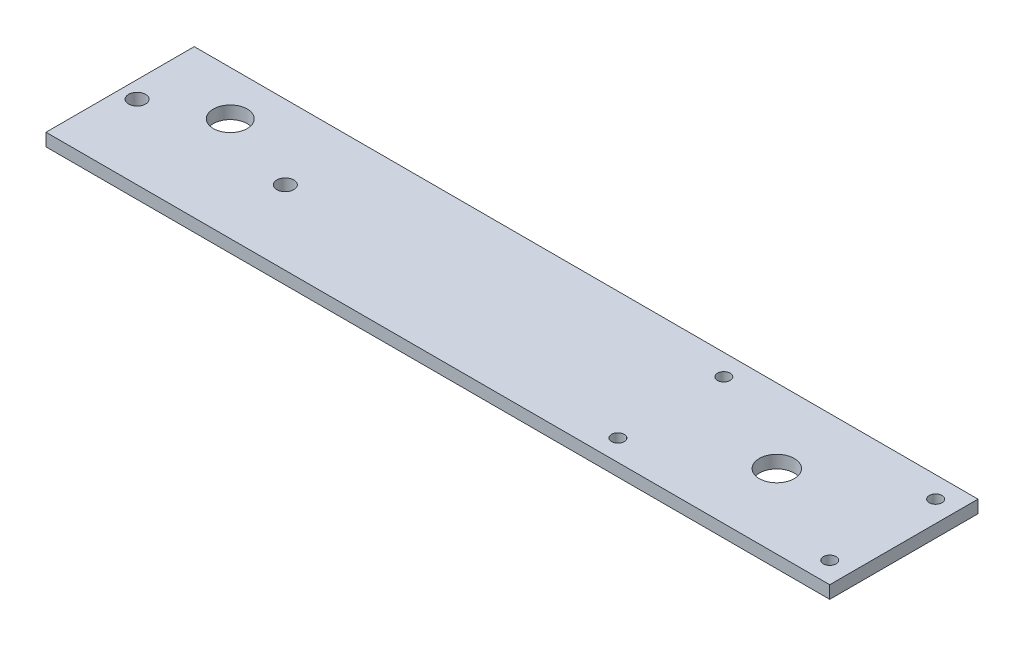
SolidWorks part; units mm, degrees
ref_plane "Front Plane" through (0, 0, 0) normal (0, 0, 1) x (1, 0, 0)
ref_plane "Top Plane" through (0, 0, 0) normal (0, 1, 0) x (1, 0, 0)
ref_plane "Right Plane" through (0, 0, 0) normal (1, 0, 0) x (0, 0, -1)
sketch "Sketch1" plane through (0, 0, 0) normal (0, 1, 0) x (1, 0, 0)
  line L1 (-92.5, 17.5) -> (92.5, 17.5)
  line L2 (-92.5, 17.5) -> (-92.5, -17.5)
  line L3 (-92.5, -17.5) -> (92.5, -17.5)
  line L4 (92.5, 17.5) -> (92.5, -17.5)
  line L5 (-92.5, 17.5) -> (92.5, -17.5) construction
  line L6 (-92.5, -17.5) -> (92.5, 17.5) construction
  circle A4 centre (62.5, 0) radius 4.125
  circle A8 centre (-88.5, 0) radius 2
  circle A9 centre (-53.5, 0) radius 2
  circle A11 centre (-73.5, 7) radius 4
  point P0 (0, 0)
  point P17 (92.5, 0)
  dimension "D3" = 30
  dimension "D4" = 17.5
  dimension "D5" = 15
  dimension "D6" = 8.25
  dimension "D7" = 7
  dimension "D8" = 8
  dimension "D1" = 35
  dimension "D2" = 185
extrude "Boss-Extrude1" add sketch "Sketch1" along normal blind 3
sketch "Sketch2" plane through (0, 3, 0) normal (0, 1, 0) x (1, 0, 0)
  line L0 (-92.5, 17.5) -> (-92.5, -17.5) construction
  line L1 (-92.5, -17.5) -> (92.5, -17.5) construction
  line L2 (-115.5, 6.5) -> (-115.5, -6.7467) construction
  circle A0 centre (-115.5, 6.5) radius 3
  circle A1 centre (-115.5, 6.5) radius 31 construction
  circle A2 centre (-27, 6.5) radius 57.5 construction
  circle A3 centre (-133, -0.5) radius 2
  circle A4 centre (-98, -0.5) radius 2
  dimension "D1" = 6
  dimension "D3" = 24
  dimension "D4" = 7
  dimension "D2" = 23
  dimension "D5" = 17.5
extrude "Cut-Extrude1" [suppressed] cut sketch "Sketch2" against normal through all contours A3 | A4
sketch "Sketch3" plane through (0, 3, 0) normal (0, 1, 0) x (1, 0, 0)
  line L0 (-92.5, -17.5) -> (92.5, -17.5) construction
  line L3 (92.5, 17.5) -> (92.5, -17.5) construction
  line L4 (-55, 0) -> (55, 0) construction
  circle A0 centre (72.5, -9.5) radius 1.5
  circle A3 centre (72.5, 9.5) radius 1.5
  dimension "D1" = 3
  dimension "D2" = 8
  dimension "D3" = 20
extrude "Cut-Extrude2" [suppressed] cut sketch "Sketch3" against normal through all
sketch "Sketch4" plane through (0, 3, 0) normal (0, 1, 0) x (1, 0, 0)
  line L0 (-92.5, 17.5) -> (92.5, 17.5) construction
  line L1 (62.5, 0) -> (41.5, 0) construction
  line L2 (92.5, 17.5) -> (92.5, -17.5) construction
  line L3 (-55, 0) -> (55, 0) construction
  circle A1 centre (52.5, 9.5) radius 1.5
  circle A2 centre (52.5, -9.5) radius 1.5
  dimension "D2" = 8
  dimension "D4" = 3
  dimension "D1" = 21
  dimension "D3" = 40
extrude "Cut-Extrude3" [suppressed] cut sketch "Sketch4" against normal through all
sketch "Sketch5" plane through (0, 3, 0) normal (0, 1, 0) x (1, 0, 0)
  line L0 (-67.865, 8.7601) -> (-83.0711, -17.5777) construction
  line L1 (-92.5, 17.5) -> (-92.5, -17.5) construction
  circle A0 centre (-73.5, 7) radius 4 construction
  circle A1 centre (-62.8075, 17.52) radius 1.5
  circle A2 centre (-77.2643, -7.52) radius 1.5
  dimension "D1" = 3
  dimension "D2" = 3
  dimension "D4" = 15
  dimension "D5" = 15
  dimension "D3" = 30
extrude "Cut-Extrude5" [suppressed] cut sketch "Sketch5" against normal through all
sketch "Sketch6" plane through (0, 3, 0) normal (0, 1, 0) x (1, 0, 0)
  line L0 (-92.5, 17.5) -> (92.5, 17.5) construction
  line L1 (92.5, 17.5) -> (92.5, -17.5) construction
  line L2 (-55, 0) -> (55, 0) construction
  line L3 (62.5, 0) -> (62.5, 14.7754) construction
  circle A0 centre (87.5, 12.5) radius 1.5
  circle A1 centre (87.5, -12.5) radius 1.5
  circle A2 centre (37.5, -12.5) radius 1.5
  circle A3 centre (37.5, 12.5) radius 1.5
  dimension "D3" = 3
  dimension "D1" = 5
  dimension "D2" = 5
extrude "Cut-Extrude6" cut sketch "Sketch6" against normal through all
sketch "Sketch7" plane through (0, 3, 0) normal (0, 1, 0) x (1, 0, 0)
  line L1 (62.5, 0) -> (87.5, 0)
  line L2 (62.5, 0) -> (62.5, 12.5)
  line L3 (62.5, 12.5) -> (87.5, 12.5)
  line L4 (87.5, 0) -> (87.5, 12.5)
